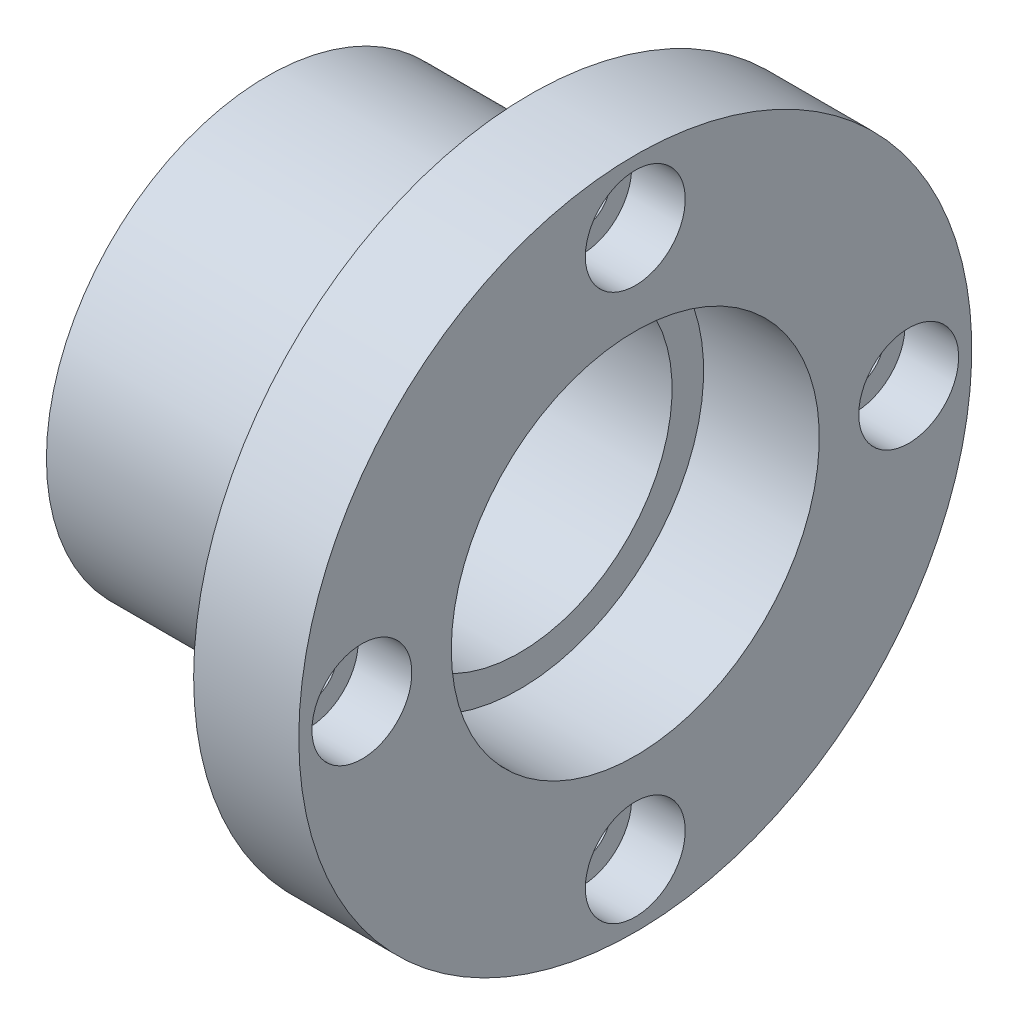
SolidWorks part; units mm, degrees
ref_plane "前视基准面" through (0, 0, 0) normal (0, 0, 1) x (1, 0, 0)
ref_plane "上视基准面" through (0, 0, 0) normal (0, 1, 0) x (1, 0, 0)
ref_plane "右视基准面" through (0, 0, 0) normal (1, 0, 0) x (0, 0, -1)
sketch "草图1" plane through (0, 0, 0) normal (0, 0, 1) x (1, 0, 0)
  line L0 (-35, 21) -> (-35, 17.5)
  line L1 (-35, 17.5) -> (-24, 17.5)
  line L2 (-24, 17.5) -> (-24, 14.5)
  line L3 (-24, 14.5) -> (-11, 14.5)
  line L4 (-11, 14.5) -> (-11, 17.5)
  line L5 (-11, 17.5) -> (0, 17.5)
  line L6 (0, 17.5) -> (0, 32)
  line L7 (0, 32) -> (-10, 32)
  line L8 (-10, 32) -> (-10, 21)
  line L9 (-10, 21) -> (-35, 21)
  line L10 (0, 0) -> (-35, 0) construction
revolve "旋转1" add sketch "草图1" angle 360 about L10 reverse direction yes
ref_plane "基准面1" through (0, 0, 0) normal (1, 0, 0) x (0, 0, -1)
ref_plane "基准面2" through (-35, 0, 0) normal (1, 0, 0) x (0, 0, -1)
ref_plane "基准面3" through (0, 0, 0) normal (0, 0, 1) x (1, 0, 0)
sketch "草图2" plane through (0, 0, 0) normal (0, 0, 1) x (1, 0, 0)
  line L0 (-10, 26) -> (-10, 28.75)
  line L1 (-10, 28.75) -> (-5.1, 28.75)
  line L2 (-5.1, 28.75) -> (-5.1, 30.75)
  line L3 (-5.1, 30.75) -> (0, 30.75)
  line L4 (0, 30.75) -> (0, 26)
  line L5 (0, 26) -> (-10, 26)
  line L6 (0, 26) -> (-10, 26) construction
revolve "切除-旋转1" cut sketch "草图2" angle 360 about L6 reverse direction yes
sketch "草图3" plane through (0, 0, 0) normal (1, 0, 0) x (0, 0, -1)
  line L0 (0, 26) -> (-707.1068, -681.1068)
  line L1 (0, 26) -> (707.1068, -681.1068)
pattern_linear "阵列(线性)1" count 2 spacing 36.7696 along (0, -0.7071, 0.7071) count 2 spacing 36.7696 along (0, -0.7071, -0.7071) of "切除-旋转1"
ref_plane "to_bearing1 XY" through (0, 0, 0) normal (1, 0, 0) x (0, 0, -1)
ref_plane "to_bearing1 XZ" through (0, 0, 0) normal (0, -1, 0) x (-1, 0, 0)
ref_plane "to_bearing1 YZ" through (0, 0, 0) normal (0, 0, -1) x (-1, 0, 0)
ref_axis "to_bearing1 X" through (0, 0, 80.9) along (0, 0, -1)
ref_axis "to_bearing1 Y" through (0, -50, 0) along (0, 1, 0)
ref_axis "to_bearing1 Z" through (80.9, 0, 0) along (-1, 0, 0)
sketch3d "to_bearing1"
  point P0 (0, 0, 0)
ref_plane "to_bearing2 XY" through (-35, 0, 0) normal (1, 0, 0) x (0, 0, -1)
ref_plane "to_bearing2 XZ" through (0, 0, 0) normal (0, -1, 0) x (-1, 0, 0)
ref_plane "to_bearing2 YZ" through (0, 0, 0) normal (0, 0, -1) x (-1, 0, 0)
ref_axis "to_bearing2 X" through (-35, 0, 80.9) along (0, 0, -1)
ref_axis "to_bearing2 Y" through (-35, -50, 0) along (0, 1, 0)
ref_axis "to_bearing2 Z" through (80.9, 0, 0) along (-1, 0, 0)
sketch3d "to_bearing2"
  point P0 (-35, 0, 0)
